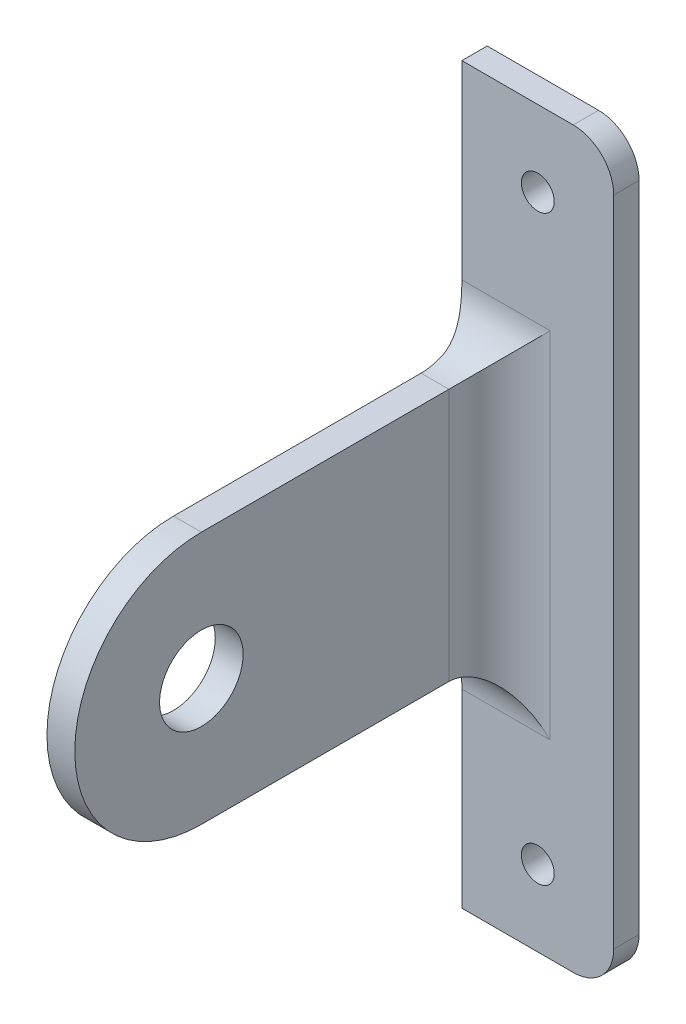
SolidWorks part; units mm, degrees
ref_plane "Front Plane" through (0, 0, 0) normal (0, 0, 1) x (1, 0, 0)
ref_plane "Top Plane" through (0, 0, 0) normal (0, 1, 0) x (1, 0, 0)
ref_plane "Right Plane" through (0, 0, 0) normal (1, 0, 0) x (0, 0, -1)
sketch "Sketch1" plane through (0, 0, 0) normal (1, 0, 0) x (0, 0, -1)
  line L1 (0, 12.5) -> (34.45, 12.5)
  line L2 (0, 4.125) -> (0, -12.5)
  line L3 (0, -12.5) -> (34.45, -12.5)
  line L4 (34.45, 12.5) -> (34.45, -12.5)
  circle A0 centre (0, 0) radius 4.125
  circle A1 centre (0, 0) radius 12.5 construction
  arc A2 (0, 12.5) -> (0, -12.5) centre (0, 0) ccw
  dimension "D1" = 8.25
  dimension "D2" = 25
  dimension "D3" = 34.45
extrude "Boss-Extrude1" add sketch "Sketch1" along normal blind 2.75 contours L1 A2 A0 L3 L4 region at (0, 0, -12.849)
sketch "Sketch2" [suppressed] plane through (0, 0, 0) normal (-1, 0, 0) x (0, 0, 1)
  circle A0 centre (0, 0) radius 1.5
  circle A1 centre (0, 0) radius 4.5
  dimension "D1" = 9
  dimension "D2" = 3
sketch "Sketch4" [suppressed] plane through (2.5, 0, 0) normal (1, 0, 0) x (0, 0, -1)
  circle A0 centre (0, 0) radius 2.5
sketch "Sketch5" [suppressed] plane through (2.5, 0, 0) normal (1, 0, 0) x (0, 0, -1)
  circle A0 centre (0, 0) radius 4.5
  circle A1 centre (0, 0) radius 2.5
  dimension "D1" = 9
  dimension "D2" = 5
sketch "Sketch6" plane through (0, 0, -34.45) normal (0, 0, -1) x (-1, 0, 0)
  line L1 (-8.8125, 36.25) -> (53.3216, 36.25)
  line L3 (6.25, -36.25) -> (53.3216, -36.25)
  line L4 (53.3216, 36.25) -> (53.3216, -36.25)
  line L6 (53.3216, -36.25) -> (-19.1784, 36.25) construction
  line L7 (6.25, -36.25) -> (-19.1784, -36.25)
  line L9 (-8.8125, 36.25) -> (-19.1784, 36.25)
  line L10 (-19.1784, -36.25) -> (-19.1784, 36.25)
  line L11 (53.3216, 36.25) -> (-19.1784, -36.25) construction
  point P4 (17.0716, 0)
  dimension "D1" = 72.5
  dimension "D2" = 72.5
extrude "Boss-Extrude4" add sketch "Sketch6" against normal blind 2.5
ref_plane "Plane1" through (-17.0716, 0, 0) normal (1, 0, 0) x (0, 0, -1)
ref_plane "Plane2" through (9.4784, 0, 0) normal (1, 0, 0) x (0, 0, -1)
sketch "Sketch7" plane through (0, 0, -31.95) normal (0, 0, 1) x (1, 0, 0)
  line L7 (1.7881, -3.3824) -> (-5.2119, -3.3824)
  line L12 (1.7881, -3.3824) -> (1.7881, -19.8824)
  line L18 (1.7881, -19.8824) -> (-5.2119, -19.8824)
  line L19 (-5.2119, -3.3824) -> (-5.2119, -19.8824)
  line L20 (1.7881, -3.3824) -> (-5.2119, -19.8824) construction
  line L21 (1.7881, -19.8824) -> (-5.2119, -3.3824) construction
  line L22 (-24.5, -4) -> (-8.5, -4)
  line L23 (-24.5, -4) -> (-24.5, 4)
  line L24 (-24.5, 4) -> (-8.5, 4)
  line L25 (-8.5, -4) -> (-8.5, 4)
  line L26 (-24.5, -4) -> (-8.5, 4) construction
  line L27 (-24.5, 4) -> (-8.5, -4) construction
  point P0 (-16.5, 0)
  point P2 (-1.7119, -11.6324)
  dimension "D1" = 16
  dimension "D2" = 16.5
  dimension "D3" = 7
  dimension "D4" = 8
extrude "Cut-Extrude2" cut sketch "Sketch7" against normal up to next
sketch "Sketch8" plane through (0, 0, 0) normal (0, 1, 0) x (1, 0, 0)
  line L10 (2.75, 4.125) -> (0, 4.125)
  line L15 (2.75, 4.125) -> (2.75, 31.95)
  line L16 (2.75, 31.95) -> (0, 31.95)
  line L21 (0, 4.125) -> (0, 31.95)
sketch "Sketch9" plane through (0, -12.5, 0) normal (0, -1, 0) x (1, 0, 0)
  line L0 (2.75, 0) -> (2.75, -31.95) construction
  line L1 (0, -31.95) -> (2.75, -31.95)
  line L2 (0, -31.95) -> (0, -9.5612)
  line L3 (0, -9.5612) -> (2.75, -9.5612)
  line L4 (2.75, -31.95) -> (2.75, -9.5612)
extrude "Cut-Extrude3" cut sketch "Sketch9" against normal up to next
extrude "Boss-Extrude5" add sketch "Sketch8" along normal mid plane 25
fillet "Fillet1" [suppressed] radius 4
fillet "Fillet2" radius 1 8 edges at (-5.2119, -3.3824, -33.2) (-5.2119, -19.8824, -33.2) (1.7881, -3.3824, -33.2) (-8.5, 4, -33.2) (1.7881, -19.8824, -33.2) (-8.5, -4, -33.2) (-24.5, 4, -33.2) (-24.5, -4, -33.2)
fillet "Fillet3" radius 4 4 edges at (19.1784, -36.25, -33.2) (19.1784, 36.25, -33.2) (-53.3216, 36.25, -33.2) (-53.3216, -36.25, -33.2)
sketch "Sketch10" plane through (0, 0, 0) normal (0, 1, 0) x (1, 0, 0)
  line L0 (15.1784, 31.95) -> (19.1784, 31.95) construction
  line L1 (21.7259, 31.95) -> (-56.5098, 31.95)
  line L2 (21.7259, 31.95) -> (21.7259, 38.24)
  line L3 (21.7259, 38.24) -> (-56.5098, 38.24)
  line L4 (-56.5098, 31.95) -> (-56.5098, 38.24)
extrude "Cut-Extrude4" cut sketch "Sketch10" against normal through all both and the other way through all
sketch "Sketch11" plane through (0, 0, 0) normal (0, 1, 0) x (1, 0, 0)
  line L1 (14.03, 31.95) -> (-0.97, 31.95)
  line L2 (14.03, 31.95) -> (14.03, 29.45)
  line L3 (14.03, 29.45) -> (-0.97, 29.45)
  line L4 (-0.97, 31.95) -> (-0.97, 29.45)
  line L6 (2.75, 31.95) -> (0, 31.95) construction
  line L7 (0, 31.95) -> (0, 0) construction
  dimension "D1" = 2.5
  dimension "D2" = 15
  dimension "D3" = 0.97
extrude "Boss-Extrude6" add sketch "Sketch11" along normal mid plane 25
sketch "Sketch12" plane through (0, 0, -31.95) normal (0, 0, -1) x (-1, 0, 0)
  line L0 (55, 0) -> (-55, 0) construction
  line L1 (-14.03, 36.25) -> (58.47, 36.25) construction
  line L2 (-14.03, 36.25) -> (-14.03, -36.25) construction
  line L3 (-14.03, -36.25) -> (58.47, -36.25) construction
  line L4 (58.47, 36.25) -> (58.47, -36.25) construction
  line L5 (-14.03, 36.25) -> (58.47, -36.25) construction
  line L6 (58.47, 36.25) -> (-14.03, -36.25) construction
  line L7 (-14.03, 12.5) -> (-14.03, -12.5) construction
  circle A0 centre (-6.53, 28.75) radius 1.5
  circle A1 centre (-6.53, -28.75) radius 1.5
  circle A2 centre (-6.53, 28.75) radius 3
  circle A3 centre (-6.53, -28.75) radius 3
  point P4 (-14.03, 0)
  dimension "D3" = 3
  dimension "D5" = 6
  dimension "D1" = 72.5
  dimension "D2" = 72.5
  dimension "D4" = 7.5
sketch "Sketch13" plane through (0, 0, -31.95) normal (0, 0, -1) x (-1, 0, 0)
  line L0 (-14.03, 12.5) -> (0.97, 12.5) construction
  line L1 (-14.03, 12.5) -> (0.97, 12.5)
  line L2 (-14.03, 12.5) -> (-14.03, 32.25)
  line L4 (0.97, 12.5) -> (0.97, 36.25)
  line L5 (0.97, 36.25) -> (-10.03, 36.25)
  arc A1 (-10.03, 36.25) -> (-14.03, 32.25) centre (-10.03, 32.25) ccw
  dimension "D2" = 4
  dimension "D1" = 4
  dimension "D3" = 15
  dimension "D4" = 36.25
  dimension "D5" = 4
extrude "Boss-Extrude7" add sketch "Sketch13" against normal blind 2.5
mirror "Mirror1" about plane through (0, 0, 0) normal (0, 1, 0) of "Boss-Extrude6", "Boss-Extrude7"
sketch "Sketch14" plane through (0, 0, -31.95) normal (0, 0, -1) x (-1, 0, 0)
  line L1 (0.97, -36.25) -> (0.97, 36.25) construction
  line L2 (0.97, 36.25) -> (-10.03, 36.25) construction
  circle A0 centre (-6.53, 28.75) radius 1.625
  dimension "D3" = 3.25
  dimension "D1" = 7.5
  dimension "D2" = 7.5
extrude "Cut-Extrude5" cut sketch "Sketch14" against normal blind 2.5
sketch "Sketch15" [suppressed] plane through (0, 0, -31.95) normal (0, 0, -1) x (-1, 0, 0)
  circle A0 centre (-6.4288, 28.75) radius 2.5
  circle A1 centre (-6.4288, 28.75) radius 4
  dimension "D1" = 8
  dimension "D2" = 5
extrude "Boss-Extrude8" [suppressed] add sketch "Sketch15" against normal blind 6
mirror "Mirror2" about plane through (0, 0, 0) normal (0, 1, 0) of "Cut-Extrude5", "Boss-Extrude8"
fillet "Fillet4" radius 5 4 edges at (1.375, -12.5, -29.45) (0, 0, -29.45) (1.375, 12.5, -29.45) (2.75, 0, -29.45)
